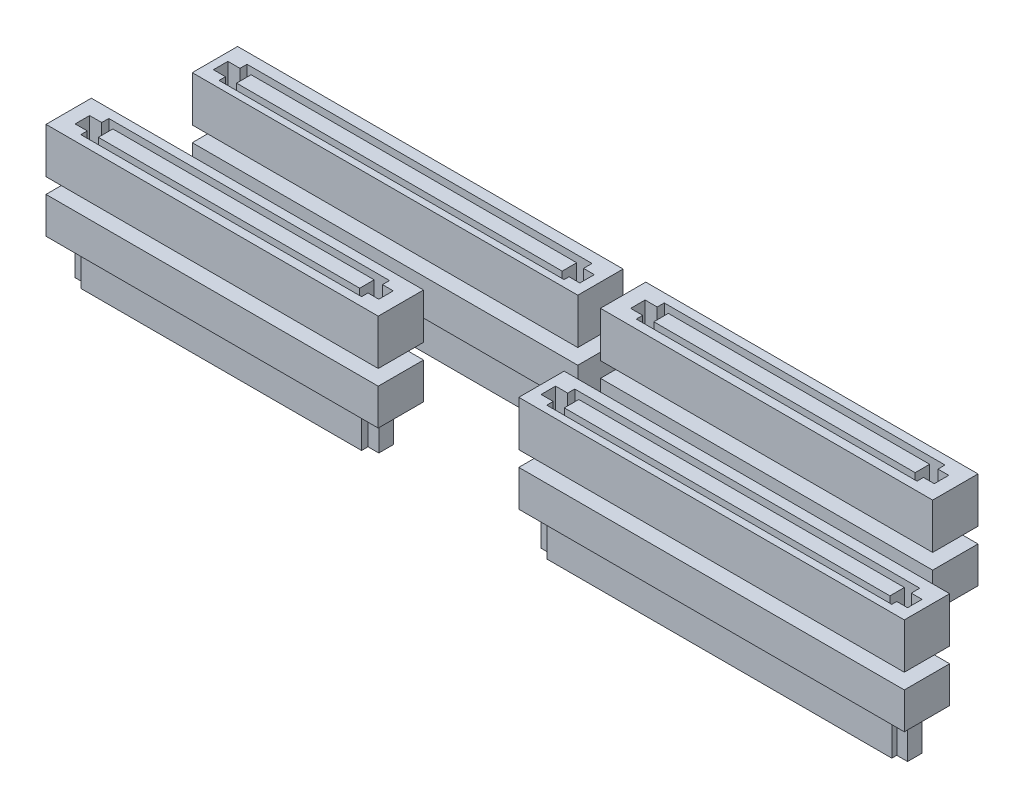
SolidWorks part; units mm, degrees
ref_plane "Front Plane" through (0, 0, 0) normal (0, 0, 1) x (1, 0, 0)
ref_plane "Top Plane" through (0, 0, 0) normal (0, 1, 0) x (1, 0, 0)
ref_plane "Right Plane" through (0, 0, 0) normal (1, 0, 0) x (0, 0, -1)
sketch "Sketch1" plane through (0, 0, 0) normal (0, 1, 0) x (1, 0, 0)
  line L0 (54.75, 9.5) -> (97.25, 9.5)
  line L1 (2.625, 9.5) -> (39.25, 9.5)
  line L2 (2.625, 9.5) -> (2.625, 4.5)
  line L3 (2.625, 4.5) -> (39.25, 4.5)
  line L4 (39.25, 9.5) -> (39.25, 4.5)
  line L5 (0, 0) -> (100, 0) construction
  line L6 (0, 0) -> (0, 75) construction
  line L7 (0, 75) -> (100, 75) construction
  line L8 (100, 0) -> (100, 75) construction
  line L9 (54.75, 9.5) -> (54.75, 4.5)
  line L10 (54.75, 4.5) -> (97.25, 4.5)
  line L11 (97.25, 9.5) -> (97.25, 4.5)
  line L12 (50.75, 22.5) -> (87.375, 22.5)
  line L13 (5.75, 22.5) -> (48.25, 22.5)
  line L14 (5.75, 22.5) -> (5.75, 17.5)
  line L15 (5.75, 17.5) -> (48.25, 17.5)
  line L16 (48.25, 22.5) -> (48.25, 17.5)
  line L17 (50.75, 22.5) -> (50.75, 17.5)
  line L18 (50.75, 17.5) -> (87.375, 17.5)
  line L19 (87.375, 22.5) -> (87.375, 17.5)
extrude "SV4" add sketch "Sketch1" along normal blind 5
sketch "Sketch3" plane through (0, 5, 0) normal (0, 1, 0) x (1, 0, 0)
  line L0 (4.1893, 7.7457) -> (5.5243, 7.7457)
  line L1 (4.1893, 8.5242) -> (37.667, 8.5242) construction
  line L2 (4.1893, 8.5242) -> (4.1893, 5.4386) construction
  line L3 (4.1893, 5.4386) -> (37.667, 5.4386) construction
  line L4 (37.667, 8.5242) -> (37.667, 5.4386) construction
  line L5 (5.5243, 7.7457) -> (5.5243, 8.5242)
  line L6 (5.5243, 8.5242) -> (36.4757, 8.5242)
  line L7 (36.4757, 8.5242) -> (36.4757, 7.7457)
  line L8 (36.4757, 7.7457) -> (37.667, 7.7457)
  line L9 (37.667, 7.7457) -> (37.667, 6.1479)
  line L10 (37.667, 6.1479) -> (36.4757, 6.1479)
  line L11 (36.4757, 6.1479) -> (36.4757, 5.4386)
  line L12 (36.4757, 5.4386) -> (5.5243, 5.4386)
  line L13 (5.5243, 5.4386) -> (5.5243, 6.1479)
  line L14 (5.5243, 6.1479) -> (4.1893, 6.1479)
  line L15 (4.1893, 6.1479) -> (4.1893, 7.7457)
  line L16 (52.4211, 20.7536) -> (53.7561, 20.7536)
  line L17 (6.7471, 7.7457) -> (35.5588, 7.7457)
  line L18 (6.7471, 7.7457) -> (6.7471, 6.1479)
  line L19 (6.7471, 6.1479) -> (35.5588, 6.1479)
  line L20 (35.5588, 7.7457) -> (35.5588, 6.1479)
  line L21 (52.4211, 21.532) -> (85.8988, 21.532) construction
  line L22 (52.4211, 21.532) -> (52.4211, 18.4464) construction
  line L23 (52.4211, 18.4464) -> (85.8988, 18.4464) construction
  line L24 (85.8988, 21.532) -> (85.8988, 18.4464) construction
  line L25 (53.7561, 20.7536) -> (53.7561, 21.532)
  line L26 (53.7561, 21.532) -> (84.7075, 21.532)
  line L27 (84.7075, 21.532) -> (84.7075, 20.7536)
  line L28 (84.7075, 20.7536) -> (85.8988, 20.7536)
  line L29 (85.8988, 20.7536) -> (85.8988, 19.1558)
  line L30 (85.8988, 19.1558) -> (84.7075, 19.1558)
  line L31 (84.7075, 19.1558) -> (84.7075, 18.4464)
  line L32 (84.7075, 18.4464) -> (53.7561, 18.4464)
  line L33 (53.7561, 18.4464) -> (53.7561, 19.1558)
  line L34 (53.7561, 19.1558) -> (52.4211, 19.1558)
  line L35 (52.4211, 19.1558) -> (52.4211, 20.7536)
  line L36 (54.9789, 20.7536) -> (83.7906, 20.7536)
  line L37 (54.9789, 20.7536) -> (54.9789, 19.1558)
  line L38 (54.9789, 19.1558) -> (83.7906, 19.1558)
  line L39 (83.7906, 20.7536) -> (83.7906, 19.1558)
  line L40 (55.7059, 7.599) -> (57.0409, 7.599)
  line L41 (55.7059, 8.3775) -> (96.2696, 8.3775) construction
  line L42 (55.7059, 8.3775) -> (55.7059, 5.2919) construction
  line L43 (55.7059, 5.2919) -> (96.2696, 5.2919) construction
  line L44 (96.2696, 8.3775) -> (96.2696, 5.2919) construction
  line L45 (57.0409, 7.599) -> (57.0409, 8.3775)
  line L46 (57.0409, 8.3775) -> (95.0783, 8.3775)
  line L47 (95.0783, 8.3775) -> (95.0783, 7.4377)
  line L48 (95.0783, 7.4377) -> (96.2696, 7.4377)
  line L49 (96.2696, 7.4377) -> (96.2696, 5.8399)
  line L50 (96.2696, 5.8399) -> (95.0783, 5.8399)
  line L51 (95.0783, 5.8399) -> (95.0783, 5.2919)
  line L52 (95.0783, 5.2919) -> (57.0409, 5.2919)
  line L53 (57.0409, 5.2919) -> (57.0409, 6.0012)
  line L54 (57.0409, 6.0012) -> (55.7059, 6.0012)
  line L55 (55.7059, 6.0012) -> (55.7059, 7.599)
  line L56 (58.2637, 7.599) -> (94.1615, 7.599)
  line L57 (58.2637, 7.599) -> (58.2637, 6.0012)
  line L58 (58.2637, 6.0012) -> (94.1615, 6.0012)
  line L59 (94.1615, 7.599) -> (94.1615, 6.0012)
  line L60 (6.6366, 20.5397) -> (7.9716, 20.5397)
  line L61 (6.6366, 21.3182) -> (47.2003, 21.3182) construction
  line L62 (6.6366, 21.3182) -> (6.6366, 18.2325) construction
  line L63 (6.6366, 18.2325) -> (47.2003, 18.2325) construction
  line L64 (47.2003, 21.3182) -> (47.2003, 18.2325) construction
  line L65 (7.9716, 20.5397) -> (7.9716, 21.3182)
  line L66 (7.9716, 21.3182) -> (46.009, 21.3182)
  line L67 (46.009, 21.3182) -> (46.009, 20.3784)
  line L68 (46.009, 20.3784) -> (47.2003, 20.3784)
  line L69 (47.2003, 20.3784) -> (47.2003, 18.7806)
  line L70 (47.2003, 18.7806) -> (46.009, 18.7806)
  line L71 (46.009, 18.7806) -> (46.009, 18.2325)
  line L72 (46.009, 18.2325) -> (7.9716, 18.2325)
  line L73 (7.9716, 18.2325) -> (7.9716, 18.9419)
  line L74 (7.9716, 18.9419) -> (6.6366, 18.9419)
  line L75 (6.6366, 18.9419) -> (6.6366, 20.5397)
  line L76 (9.1944, 20.5397) -> (45.0922, 20.5397)
  line L77 (9.1944, 20.5397) -> (9.1944, 18.9419)
  line L78 (9.1944, 18.9419) -> (45.0922, 18.9419)
  line L79 (45.0922, 20.5397) -> (45.0922, 18.9419)
extrude "Cut-Extrude1" cut sketch "Sketch3" against normal blind 4
ref_plane "Plane1" through (0, -1.6866, 0) normal (0, 1, 0) x (1, 0, 0)
sketch "Sketch6" plane through (0, -1.6866, 0) normal (0, 1, 0) x (1, 0, 0)
  line L1 (5.75, 22.5) -> (48.25, 22.5)
  line L2 (5.75, 22.5) -> (5.75, 17.5)
  line L3 (5.75, 17.5) -> (48.25, 17.5)
  line L4 (48.25, 22.5) -> (48.25, 17.5)
  line L5 (50.75, 22.5) -> (87.375, 22.5)
  line L6 (50.75, 22.5) -> (50.75, 17.5)
  line L7 (50.75, 17.5) -> (87.375, 17.5)
  line L8 (87.375, 22.5) -> (87.375, 17.5)
  line L9 (97.25, 9.5) -> (54.75, 9.5)
  line L10 (97.25, 9.5) -> (97.25, 4.5)
  line L11 (97.25, 4.5) -> (54.75, 4.5)
  line L12 (54.75, 9.5) -> (54.75, 4.5)
  line L13 (39.25, 9.5) -> (2.625, 9.5)
  line L14 (39.25, 9.5) -> (39.25, 4.5)
  line L15 (39.25, 4.5) -> (2.625, 4.5)
  line L16 (2.625, 9.5) -> (2.625, 4.5)
extrude "SV(a)" add sketch "Sketch6" against normal blind 4 separate body
sketch "Sketch7" plane through (0, -5.6866, 0) normal (0, -1, 0) x (1, 0, 0)
  line L0 (7.9716, -21.3182) -> (7.9716, -20.5397)
  line L1 (7.9716, -20.5397) -> (6.6366, -20.5397)
  line L2 (6.6366, -20.5397) -> (6.6366, -18.9419)
  line L3 (6.6366, -18.9419) -> (7.9716, -18.9419)
  line L4 (7.9716, -18.9419) -> (7.9716, -18.2325)
  line L6 (7.9716, -18.2325) -> (46.009, -18.2325)
  line L7 (46.009, -18.2325) -> (46.009, -18.7806)
  line L8 (46.009, -18.7806) -> (47.2003, -18.7806)
  line L9 (47.2003, -18.7806) -> (47.2003, -20.3784)
  line L10 (47.2003, -20.3784) -> (46.009, -20.3784)
  line L11 (46.009, -20.3784) -> (46.009, -21.3182)
  line L12 (46.009, -21.3182) -> (7.9716, -21.3182)
  line L13 (53.7561, -21.532) -> (84.7075, -21.532)
  line L14 (9.1944, -20.5397) -> (45.0922, -20.5397)
  line L15 (9.1944, -20.5397) -> (9.1944, -18.9419)
  line L16 (9.1944, -18.9419) -> (45.0922, -18.9419)
  line L17 (45.0922, -20.5397) -> (45.0922, -18.9419)
  line L18 (54.9789, -20.7536) -> (83.7906, -20.7536)
  line L19 (54.9789, -20.7536) -> (54.9789, -19.1558)
  line L20 (54.9789, -19.1558) -> (83.7906, -19.1558)
  line L21 (83.7906, -20.7536) -> (83.7906, -19.1558)
  line L22 (94.1615, -7.599) -> (58.2637, -7.599)
  line L23 (94.1615, -7.599) -> (94.1615, -6.0012)
  line L24 (94.1615, -6.0012) -> (58.2637, -6.0012)
  line L25 (58.2637, -7.599) -> (58.2637, -6.0012)
  line L26 (35.5588, -7.7457) -> (6.7471, -7.7457)
  line L27 (35.5588, -7.7457) -> (35.5588, -6.1479)
  line L28 (35.5588, -6.1479) -> (6.7471, -6.1479)
  line L29 (6.7471, -7.7457) -> (6.7471, -6.1479)
  line L30 (84.7075, -21.532) -> (84.7075, -20.7536)
  line L31 (84.7075, -20.7536) -> (85.8988, -20.7536)
  line L32 (85.8988, -20.7536) -> (85.8988, -19.1558)
  line L33 (85.8988, -19.1558) -> (84.7075, -19.1558)
  line L34 (84.7075, -19.1558) -> (84.7075, -18.4464)
  line L35 (84.7075, -18.4464) -> (53.7561, -18.4464)
  line L36 (53.7561, -18.4464) -> (53.7561, -19.1558)
  line L37 (53.7561, -19.1558) -> (52.4211, -19.1558)
  line L38 (52.4211, -19.1558) -> (52.4211, -20.7536)
  line L39 (52.4211, -20.7536) -> (53.7561, -20.7536)
  line L40 (53.7561, -20.7536) -> (53.7561, -21.532)
  line L41 (57.0409, -8.3775) -> (57.0409, -7.599)
  line L42 (57.0409, -7.599) -> (55.7059, -7.599)
  line L43 (55.7059, -7.599) -> (55.7059, -6.0012)
  line L44 (55.7059, -6.0012) -> (57.0409, -6.0012)
  line L45 (57.0409, -6.0012) -> (57.0409, -5.2919)
  line L46 (57.0409, -5.2919) -> (95.0783, -5.2919)
  line L47 (95.0783, -5.2919) -> (95.0783, -5.8399)
  line L48 (95.0783, -5.8399) -> (96.2696, -5.8399)
  line L49 (96.2696, -5.8399) -> (96.2696, -7.4377)
  line L50 (96.2696, -7.4377) -> (95.0783, -7.4377)
  line L51 (95.0783, -7.4377) -> (95.0783, -8.3775)
  line L52 (95.0783, -8.3775) -> (57.0409, -8.3775)
  line L53 (4.1893, -6.1479) -> (5.5243, -6.1479)
  line L54 (5.5243, -6.1479) -> (5.5243, -5.4386)
  line L55 (5.5243, -5.4386) -> (36.4757, -5.4386)
  line L56 (36.4757, -5.4386) -> (36.4757, -6.1479)
  line L57 (36.4757, -6.1479) -> (37.667, -6.1479)
  line L58 (37.667, -6.1479) -> (37.667, -7.7457)
  line L59 (37.667, -7.7457) -> (36.4757, -7.7457)
  line L60 (36.4757, -7.7457) -> (36.4757, -8.5242)
  line L61 (36.4757, -8.5242) -> (5.5243, -8.5242)
  line L62 (5.5243, -8.5242) -> (5.5243, -7.7457)
  line L63 (5.5243, -7.7457) -> (4.1893, -7.7457)
  line L64 (4.1893, -7.7457) -> (4.1893, -6.1479)
extrude "SV(b)" add sketch "Sketch7" along normal blind 4
